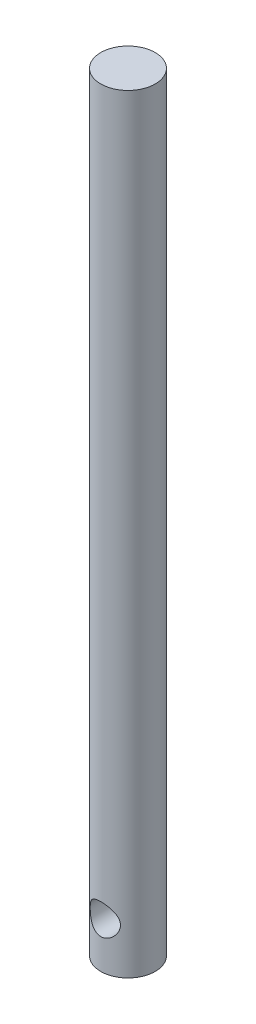
SolidWorks part; units mm, degrees
ref_plane "Front Plane" through (0, 0, 0) normal (0, 0, 1) x (1, 0, 0)
ref_plane "Top Plane" through (0, 0, 0) normal (0, 1, 0) x (1, 0, 0)
ref_plane "Right Plane" through (0, 0, 0) normal (1, 0, 0) x (0, 0, -1)
sketch "Sketch5" plane through (0, 0, 0) normal (0, 1, 0) x (1, 0, 0)
  circle A0 centre (32.6665, 0) radius 9
extrude "Boss-Extrude2" add sketch "Sketch5" along normal blind 254 separate body
ref_plane "Plane1" through (0, 0, 9) normal (0, 0, 1) x (1, 0, 0)
sketch "Sketch7" plane through (0, 0, 9) normal (0, 0, 1) x (1, 0, 0)
  line L0 (41.6665, 0) -> (23.6665, 0)
  line L1 (13.2, 0) -> (-13.2, 0) construction
  line L2 (41.6665, 0) -> (41.6665, 254) construction
  line L3 (23.6665, 254) -> (23.6665, 0) construction
  line L4 (32.6665, 0) -> (32.6665, 15) construction
  circle A0 centre (32.6665, 15) radius 5
extrude "Cut-Extrude2" cut sketch "Sketch7" against normal blind 50 contours A0 region at (32.6665, 15, 9)
